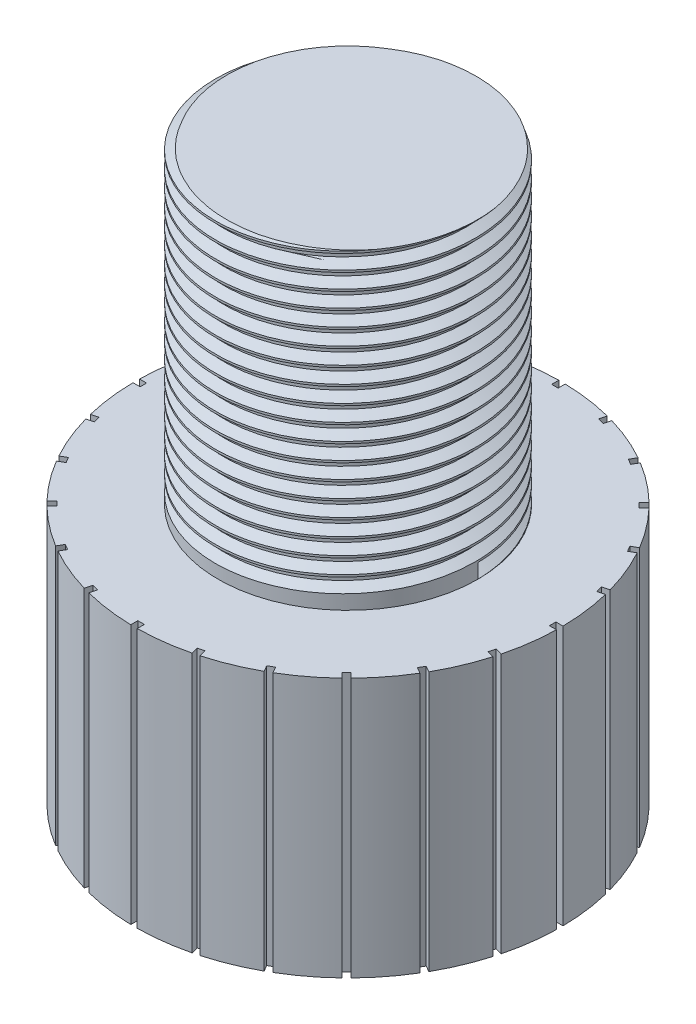
SolidWorks part; units mm, degrees
ref_plane "前视基准面" through (0, 0, 0) normal (0, 0, 1) x (1, 0, 0)
ref_plane "上视基准面" through (0, 0, 0) normal (0, 1, 0) x (1, 0, 0)
ref_plane "右视基准面" through (0, 0, 0) normal (1, 0, 0) x (0, 0, -1)
sketch "草图1" plane through (0, 0, 0) normal (0, 1, 0) x (1, 0, 0)
  circle A0 centre (0, 0) radius 4.1
  dimension "D1" = 8.2
extrude "凸台-拉伸1" add sketch "草图1" along normal blind 5
sketch "草图2" plane through (0, 5, 0) normal (0, 1, 0) x (1, 0, 0)
  circle A0 centre (0, 0) radius 2.5
  dimension "D1" = 5
extrude "凸台-拉伸2" add sketch "草图2" along normal blind 6
thread "螺纹线1" pitch 0.3175 method cut profile "螺纹线轮廓2" start angle 0, offset 0, length 10, pitch 0.3175, diameter 5
ref_plane "基准面2" through (2.5, 5, 0) normal (0, 0, 1) x (1, 0, 0)
sketch "螺纹线轮廓2" plane through (2.5, 5, 0) normal (0, 0, 1) x (1, 0, 0)
  line L0 (0, 0) -> (0, 0.3175) construction
  line L11 (0, 0) -> (0, 0.2778)
  line L12 (0, 0.2778) -> (-0.1719, 0.1786)
  line L13 (-0.1719, 0.1786) -> (-0.1719, 0.0992)
  line L15 (-0.1719, 0.0992) -> (0, 0)
  line L17 (-0.1719, 0.1389) -> (0, 0.1389) construction
  point P2 (0, 0)
  dimension "Pitch" = 0.3175
  dimension "Profile_Angle" = 60
  dimension "Profile_Land" = 0.0794
  dimension "Profile_Height" = 0.1719
sketch "草图7" plane through (0, 0, 0) normal (0, -1, 0) x (-1, 0, 0)
  line L1 (-2.3094, 0) -> (-1.1547, -2)
  line L2 (-1.1547, -2) -> (1.1547, -2)
  line L3 (1.1547, -2) -> (2.3094, 0)
  line L4 (2.3094, 0) -> (1.1547, 2)
  line L5 (1.1547, 2) -> (-1.1547, 2)
  line L6 (-1.1547, 2) -> (-2.3094, 0)
  circle A0 centre (0, 0) radius 2 construction
  dimension "D1" = 4
extrude "切除-拉伸1" cut sketch "草图7" against normal blind 1
sketch "草图8" plane through (0, 0, 0) normal (0, -1, 0) x (-1, 0, 0)
  line L1 (-4.2256, -0.0842) -> (-3.9632, -0.0842)
  line L2 (-4.2256, -0.0842) -> (-4.2256, 0.0411)
  line L3 (-4.2256, 0.0411) -> (-3.9632, 0.0411)
  line L4 (-3.9632, -0.0842) -> (-3.9632, 0.0411)
extrude "切除-拉伸2" cut sketch "草图8" against normal blind 5
sketch "草图9" plane through (0, 0, 0) normal (0, 0, 1) x (1, 0, 0)
  line L0 (0, 0) -> (0, 2.7041) construction
pattern_circular "阵列(圆周)1" count 24 over 360 about axis through (0, 0, 0) along (0, 1, 0) of "切除-拉伸2" reverse direction yes
